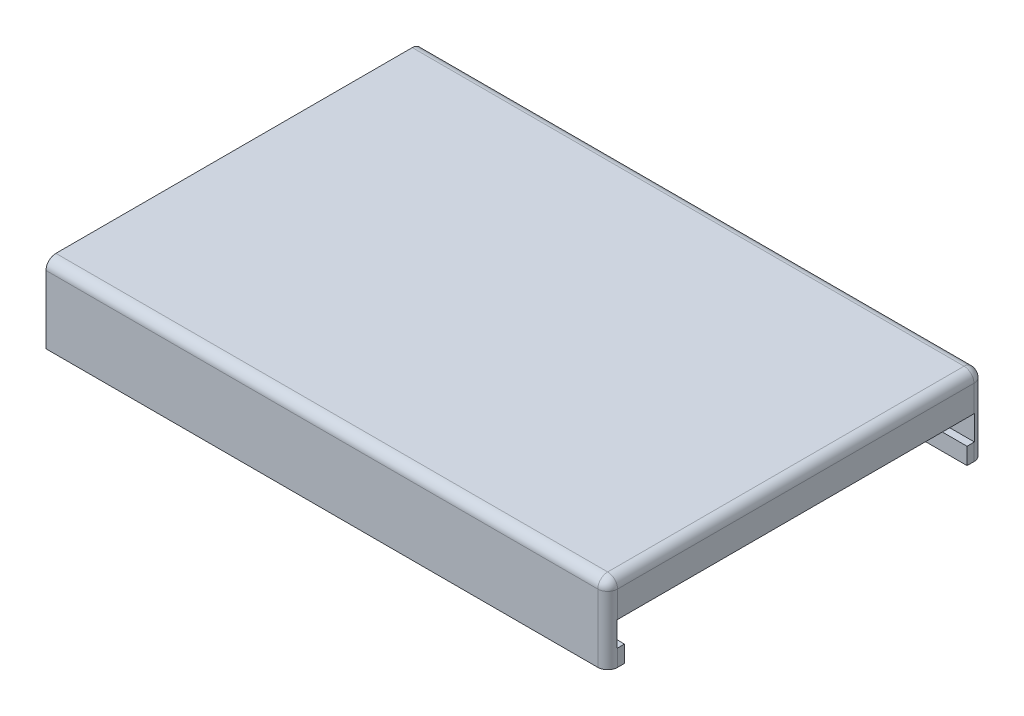
SolidWorks part; units mm, degrees
ref_plane "Front" through (0, 0, 0) normal (0, 0, 1) x (1, 0, 0)
ref_plane "Top" through (0, 0, 0) normal (0, 1, 0) x (1, 0, 0)
ref_plane "Right" through (0, 0, 0) normal (1, 0, 0) x (0, 0, -1)
sketch "Sketch1" plane through (0, 0, 0) normal (0, 1, 0) x (1, 0, 0)
  line L1 (-28.448, 19.05) -> (28.448, 19.05)
  line L2 (-28.448, 19.05) -> (-28.448, -19.05)
  line L3 (-28.448, -19.05) -> (28.448, -19.05)
  line L4 (28.448, 19.05) -> (28.448, -19.05)
  line L5 (-28.448, 19.05) -> (28.448, -19.05) construction
  line L6 (-28.448, -19.05) -> (28.448, 19.05) construction
  point P0 (0, 0)
  dimension "D1" = 56.896
  dimension "D2" = 38.1
extrude "Boss-Extrude1" add sketch "Sketch1" along normal mid plane 7.874
sketch "Sketch2" plane through (28.448, 0, 0) normal (1, 0, 0) x (0, 0, -1)
  line L1 (-19.05, -3.937) -> (19.05, -3.937) construction
  line L2 (0, -3.444) -> (0, 2.7746) construction
  line L3 (17.4928, 0.263) -> (18.0975, -2.237) construction
  line L4 (17.35, -2.237) -> (18.0975, 0.263) construction
  line L5 (18.0975, -2.237) -> (18.0975, 0.263)
  line L6 (17.4928, 0.263) -> (18.0975, 0.263)
  line L7 (-17.35, -2.237) -> (-18.0975, -2.237)
  line L8 (-19.05, 3.937) -> (-19.05, -3.937) construction
  line L9 (-17.4928, 0.263) -> (-18.0975, 0.263)
  line L10 (-18.0975, -2.237) -> (-18.0975, 0.263)
  line L11 (-17.35, -2.237) -> (-18.0975, 0.263) construction
  line L12 (-17.4928, 0.263) -> (-18.0975, -2.237) construction
  line L14 (17.35, -2.237) -> (18.0975, -2.237)
  line L16 (-17.4928, 0.263) -> (17.4928, 0.263)
  line L17 (-17.35, -2.237) -> (-17.35, -3.937)
  line L18 (-17.35, -3.937) -> (17.35, -3.937)
  line L19 (17.35, -2.237) -> (17.35, -3.937)
  line L20 (-17.4928, 0.263) -> (17.35, -3.937) construction
  line L21 (-17.35, -3.937) -> (17.4928, 0.263) construction
  point P9 (-17.7632, -0.855)
  point P16 (17.7632, -0.855)
  point P21 (0, -1.8456)
  dimension "D1" = 1.7
  dimension "D2" = 2.5
  dimension "D3" = 1.7
  dimension "D4" = 0.9525
extrude "Cut-Extrude1" cut sketch "Sketch2" against normal through all
fillet "Fillet1" radius 1 5 edges at (0, 3.937, -19.05) (28.448, 3.937, 0) (0, 3.937, 19.05) (28.448, 0, -19.05) (28.448, 0, 19.05)
sketch "Sketch3" plane through (-28.448, 0, 0) normal (-1, 0, 0) x (0, 0, 1)
  line L0 (-18.05, 3.937) -> (18.05, 3.937) construction
  line L1 (-17.35, -2.237) -> (17.4179, -2.237)
  line L2 (-17.35, -2.237) -> (-17.35, 1.937)
  line L3 (-17.35, 1.937) -> (17.4179, 1.937)
  line L4 (17.4179, -2.237) -> (17.4179, 1.937)
  line L5 (-17.35, -2.237) -> (17.4179, 1.937) construction
  line L6 (-17.35, 1.937) -> (17.4179, -2.237) construction
  point P4 (0.0339, -0.15)
  dimension "D1" = 2
extrude "Cut-Extrude2" cut sketch "Sketch3" against normal offset from surface (54.896 mm away) 2 up to face at (28.448, 1.6, 0)
